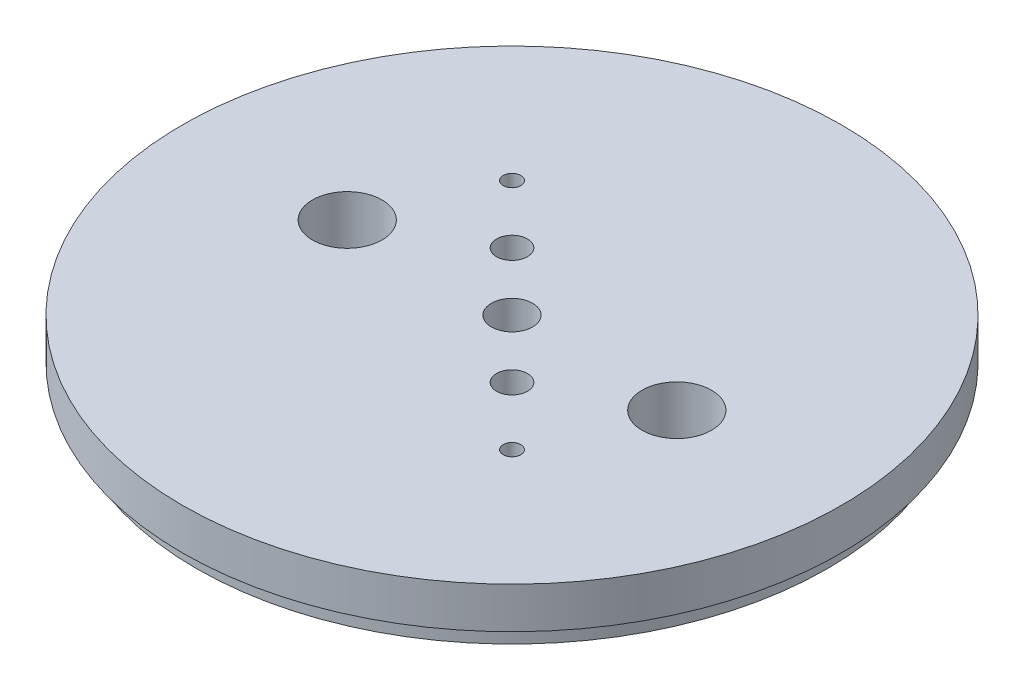
SolidWorks part; units mm, degrees
material "6061-T4 (SS)"
ref_plane "Front Plane" through (0, 0, 0) normal (0, 0, 1) x (1, 0, 0)
ref_plane "Top Plane" through (0, 0, 0) normal (0, 1, 0) x (1, 0, 0)
ref_plane "Right Plane" through (0, 0, 0) normal (1, 0, 0) x (0, 0, -1)
sketch "Sketch1" plane through (0, 0, 0) normal (0, 1, 0) x (1, 0, 0)
  line L0 (0, -50.8) -> (0, 50.8) construction
  line L1 (-50.8, 0) -> (50.8, 0) construction
  line L2 (-17.9605, 17.9605) -> (0, 0) construction
  line L3 (0, 56.7387) -> (0, 29.6936) construction
  line L4 (3.6407, 56.7387) -> (3.6407, 29.6936) construction
  line L5 (-3.6407, 56.7387) -> (-3.6407, 29.6936) construction
  line L6 (0, -56.7387) -> (0, -29.6936) construction
  line L7 (3.6407, -56.7387) -> (3.6407, -29.6936) construction
  line L8 (-3.6407, -56.7387) -> (-3.6407, -29.6936) construction
  line L9 (-35.921, -35.921) -> (54.3236, 54.3236) construction
  circle A0 centre (0, 0) radius 50.8
  circle A1 centre (0, 0) radius 3.175
  circle A2 centre (25.4, 0) radius 5.3578
  circle A3 centre (-25.4, 0) radius 5.3578
  circle A4 centre (-17.9605, 17.9605) radius 1.3589
  arc A6 (3.6407, 56.7387) -> (-3.6407, 56.7387) centre (0, 56.7387) ccw construction
  arc A7 (-3.6407, 29.6936) -> (3.6407, 29.6936) centre (0, 29.6936) ccw construction
  arc A8 (3.6407, -56.7387) -> (-3.6407, -56.7387) centre (0, -56.7387) cw construction
  arc A9 (-3.6407, -29.6936) -> (3.6407, -29.6936) centre (0, -29.6936) cw construction
  circle A10 centre (17.9605, -17.9605) radius 1.3589
  circle A11 centre (-8.9803, 8.9803) radius 2.3813
  circle A12 centre (8.9803, -8.9803) radius 2.3813
  point P16 (0, 43.2162)
  point P19 (0, 0)
  point P26 (0, -43.2162)
  dimension "D1" = 101.6
  dimension "D2" = 6.35
  dimension "D3" = 10.7156
  dimension "D5" = 2.7178
  dimension "D8" = 4.7625
  dimension "D6" = 25.4
  dimension "D7" = 45
  dimension "D4" = 45
  dimension "D9" = 25.4
extrude "Boss-Extrude1" add sketch "Sketch1" along normal blind 9.525
sketch "Sketch2" plane through (0, 0, 0) normal (0, -1, 0) x (1, 0, 0)
  circle A0 centre (0, 0) radius 50.8
  circle A1 centre (0, 0) radius 48.641
  dimension "D1" = 101.6
  dimension "D2" = 97.282
extrude "Cut-Extrude1" cut sketch "Sketch2" against normal blind 3.175
sketch "Sketch3" plane through (0, 9.525, 0) normal (0, 1, 0) x (1, 0, 0)
  line L0 (0, 50.8) -> (0, -50.8) construction
  line L1 (-50.8, 0) -> (50.8, 0) construction
  line L2 (0, 34.798) -> (0, 13.97) construction
  line L3 (3.2385, 34.798) -> (3.2385, 13.97)
  line L4 (-3.2385, 34.798) -> (-3.2385, 13.97)
  line L5 (0, -34.798) -> (0, -13.97) construction
  line L6 (3.2385, -34.798) -> (3.2385, -13.97)
  line L7 (-3.2385, -34.798) -> (-3.2385, -13.97)
  circle A0 centre (0, 0) radius 50.8 construction
  arc A1 (3.2385, 34.798) -> (-3.2385, 34.798) centre (0, 34.798) ccw
  arc A2 (-3.2385, 13.97) -> (3.2385, 13.97) centre (0, 13.97) ccw
  arc A3 (3.2385, -34.798) -> (-3.2385, -34.798) centre (0, -34.798) cw
  arc A4 (-3.2385, -13.97) -> (3.2385, -13.97) centre (0, -13.97) cw
  point P7 (0, 13.97)
  point P8 (0, 34.798)
  point P12 (0, 24.384)
  point P20 (0, -24.384)
  point P25 (0, -34.798)
  point P26 (0, -13.97)
  dimension "D1" = 13.97
  dimension "D2" = 20.828
  dimension "D3" = 6.477
extrude "Cut-Extrude2" cut sketch "Sketch3" against normal blind 3.556 from offset 5.969 offset against normal yes
equation "\"Lead_Screw_Dist\" = 2in"
equation "\"Coupler_OD\" = 3.899in"
equation "\"Coupler_ID\" = 3.755in"
equation "\"Lead_Screw_Hole_Diam\" = (27/64)*1in"
equation "\"D3@Sketch1\"=\"Lead_Screw_Hole_Diam\""
equation "\"D9@Sketch1\"=\"Lead_Screw_Dist\"/2"
